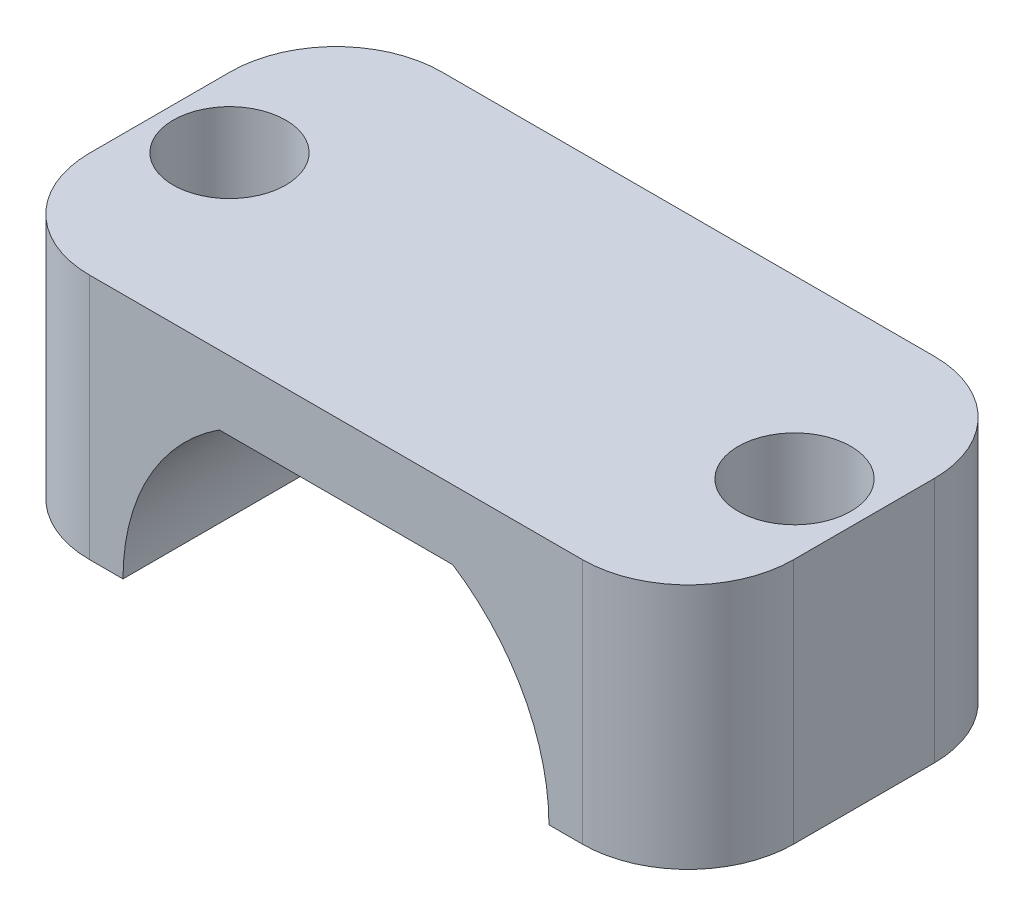
SolidWorks part; units mm, degrees
ref_plane "Front Plane" through (0, 0, 0) normal (0, 0, 1) x (1, 0, 0)
ref_plane "Top Plane" through (0, 0, 0) normal (0, 1, 0) x (1, 0, 0)
ref_plane "Right Plane" through (0, 0, 0) normal (1, 0, 0) x (0, 0, -1)
sketch "Sketch1" plane through (0, 0, 0) normal (0, 0, 1) x (1, 0, 0)
  line L0 (-10, 0) -> (10, 0)
  line L1 (10, 0) -> (10, -7)
  line L2 (10, -7) -> (6.05, -7)
  line L3 (3.315, -1.9661) -> (-3.315, -1.9661)
  line L4 (-6.05, -7) -> (-10, -7)
  line L5 (-10, -7) -> (-10, 0)
  arc A0 (6.05, -7) -> (3.315, -1.9661) centre (0.05, -7) ccw
  arc A1 (-3.315, -1.9661) -> (-6.05, -7) centre (-0.05, -7) ccw
  point P4 (0, 0)
  point P12 (0, -1.9661)
  dimension "D1" = 6
  dimension "D2" = 6.63
  dimension "D3" = 20
  dimension "D4" = 12.1
  dimension "D5" = 7
extrude "Boss-Extrude1" add sketch "Sketch1" along normal mid plane 10
sketch "Sketch2" plane through (0, -7, 0) normal (0, -1, 0) x (1, 0, 0)
  line L0 (6.05, 5) -> (10, 5) construction
  line L1 (-10, 5) -> (-6.05, 5) construction
  circle A0 centre (8.025, 0) radius 1.6
  circle A1 centre (-8.025, 0) radius 1.6
  point P10 (8.025, 5)
  point P14 (-8.025, 5)
  dimension "D1" = 3.2
extrude "Cut-Extrude1" cut sketch "Sketch2" against normal through all
fillet "Fillet3" radius 3 4 edges at (10, -3.5, -5) (10, -3.5, 5) (-10, -3.5, -5) (-10, -3.5, 5)
